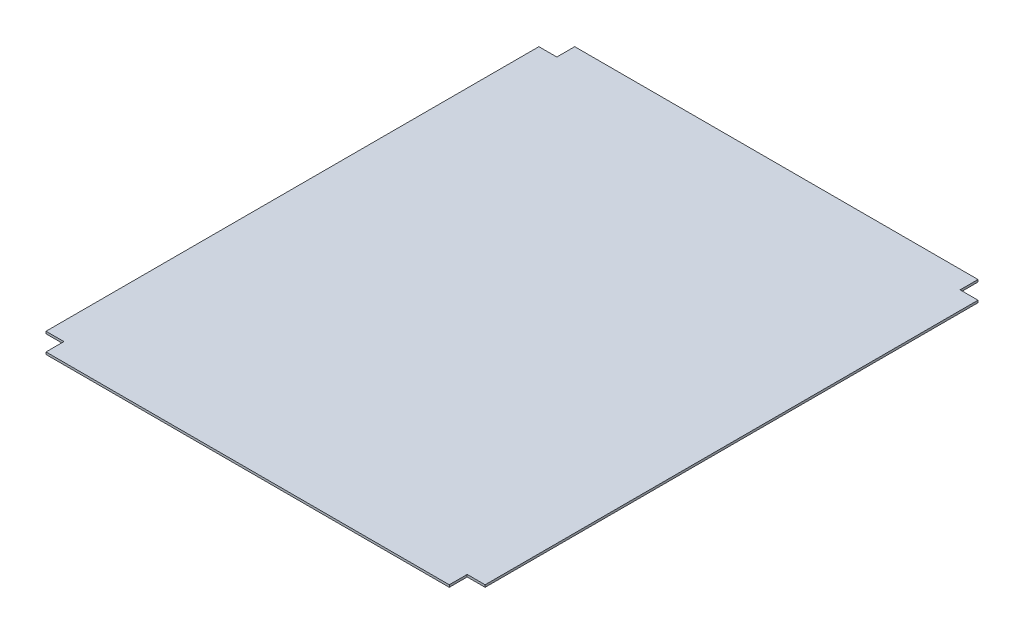
SolidWorks part; units mm, degrees
ref_plane "Front Plane" through (0, 0, 0) normal (0, 0, 1) x (1, 0, 0)
ref_plane "Top Plane" through (0, 0, 0) normal (0, 1, 0) x (1, 0, 0)
ref_plane "Right Plane" through (0, 0, 0) normal (1, 0, 0) x (0, 0, -1)
sketch "Sketch1" plane through (0, 0, 0) normal (0, 1, 0) x (1, 0, 0)
  line L1 (-622.3, -749.3) -> (622.3, -749.3)
  line L2 (-622.3, -749.3) -> (-622.3, 749.3)
  line L3 (-622.3, 749.3) -> (622.3, 749.3)
  line L4 (622.3, -749.3) -> (622.3, 749.3)
  line L5 (-622.3, -749.3) -> (622.3, 749.3) construction
  line L6 (-622.3, 749.3) -> (622.3, -749.3) construction
  point P0 (0, 0)
  dimension "D1" = 1244.6
  dimension "D2" = 1498.6
extrude "Boss-Extrude1" add sketch "Sketch1" along normal mid plane 6.35
sketch "Sketch2" plane through (0, 3.175, 0) normal (0, 1, 0) x (1, 0, 0)
  line L0 (0, 749.3) -> (0, -749.3) construction
  line L1 (-622.3, 749.3) -> (-571.5, 749.3)
  line L2 (-622.3, 749.3) -> (-622.3, 698.5)
  line L3 (-622.3, 698.5) -> (-571.5, 698.5)
  line L4 (-571.5, 749.3) -> (-571.5, 698.5)
  line L5 (622.3, 749.3) -> (-622.3, 749.3) construction
  line L6 (-622.3, -749.3) -> (622.3, -749.3) construction
  line L7 (622.3, 0) -> (-622.3, 0) construction
  line L8 (622.3, -749.3) -> (622.3, 749.3) construction
  line L9 (-622.3, 749.3) -> (-622.3, -749.3) construction
  line L10 (571.5, 749.3) -> (571.5, 698.5)
  line L11 (622.3, 698.5) -> (571.5, 698.5)
  line L12 (622.3, 749.3) -> (622.3, 698.5)
  line L13 (622.3, 749.3) -> (571.5, 749.3)
  line L14 (622.3, -749.3) -> (571.5, -749.3)
  line L15 (622.3, -749.3) -> (622.3, -698.5)
  line L16 (622.3, -698.5) -> (571.5, -698.5)
  line L17 (571.5, -749.3) -> (571.5, -698.5)
  line L18 (-571.5, -749.3) -> (-571.5, -698.5)
  line L19 (-622.3, -698.5) -> (-571.5, -698.5)
  line L20 (-622.3, -749.3) -> (-622.3, -698.5)
  line L21 (-622.3, -749.3) -> (-571.5, -749.3)
  dimension "D1" = 50.8
extrude "Cut-Extrude1" cut sketch "Sketch2" against normal through all
equation "\"width\"= 48in"
equation "\"length\"= 58in"
equation "\"square tubing width\"= 2in"
equation "\"D1@Sketch2\"=\"square tubing width\""
